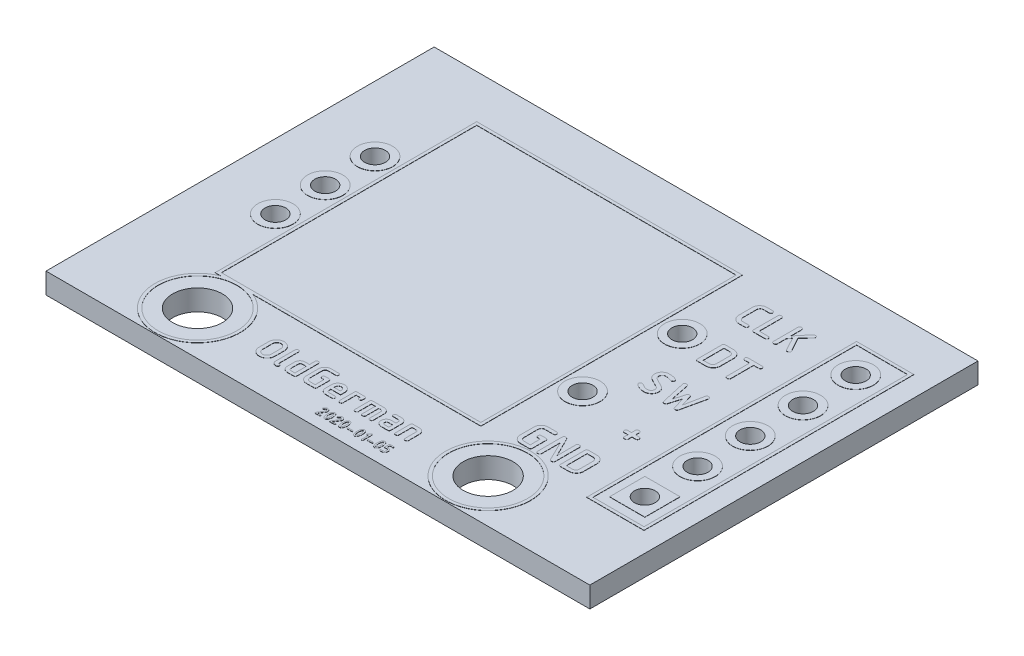
SolidWorks part; units mm, degrees
ref_plane "Front" through (0, 0, 0) normal (0, 0, 1) x (1, 0, 0)
ref_plane "Top" through (0, 0, 0) normal (0, 1, 0) x (1, 0, 0)
ref_plane "Right" through (0, 0, 0) normal (1, 0, 0) x (0, 0, -1)
sketch "草图1" plane through (0, 0, 0) normal (0, 1, 0) x (1, 0, 0)
  line L1 (0, 0) -> (26.2, 0)
  line L2 (0, 0) -> (0, 18.7)
  line L3 (0, 18.7) -> (26.2, 18.7)
  line L4 (26.2, 0) -> (26.2, 18.7)
  circle A0 centre (19.2, 2.1) radius 1.2
  circle A1 centre (5.2, 2.1) radius 1.2
  circle A2 centre (23.85, 5) radius 0.5
  circle A3 centre (23.85, 7.54) radius 0.5
  circle A4 centre (23.85, 10.08) radius 0.5
  circle A5 centre (23.85, 12.62) radius 0.5
  circle A6 centre (23.85, 15.16) radius 0.5
  dimension "D3" = 2.4
  dimension "D4" = 2.4
  dimension "D9" = 1
  dimension "D12" = 5
  dimension "D1" = 26.2
  dimension "D2" = 18.7
  dimension "D5" = 7
  dimension "D6" = 14
  dimension "D7" = 5.2
  dimension "D8" = 16.6
  dimension "D10" = 2.35
  dimension "D11" = 5
extrude "凸台-拉伸1" add sketch "草图1" along normal blind 0.5 and the other way blind 0.5
sketch "草图2" plane through (0, -0.5, 0) normal (0, -1, 0) x (1, 0, 0)
  line L0 (3.15, -7.5) -> (3.15, -13.705) construction
  line L1 (3.25, -7.5) -> (3.05, -7.5) construction
  line L2 (3.05, -7.9) -> (3.8248, -7.9) construction
  line L3 (3.05, -8.3) -> (3.05, -7.5) construction
  line L4 (3.15, -7.9) -> (17.95, -7.9) construction
  line L5 (3.15, -7.9) -> (3.15, -10.3) construction
  circle A0 centre (3.15, -7.9) radius 0.4994
  circle A1 centre (17.95, -7.9) radius 0.4994
  circle A3 centre (17.95, -12.7) radius 0.4994
  circle A4 centre (3.15, -10.3) radius 0.4994
  circle A5 centre (3.15, -12.7) radius 0.4994
  circle A42 centre (17.95, -10.3) radius 0.4994 [skipped]
  dimension "D1" = 0.9989
  dimension "D2" = 2
  dimension "D4" = 14.8
  dimension "D5" = 2.4
  dimension "D3" = 3
extrude "切除-拉伸1" cut sketch "草图2" against normal blind 2
sketch "草图6" plane through (0, 0.5, 0) normal (0, 1, 0) x (1, 0, 0)
  line L1 (24.6991, 4.15) -> (23.0009, 4.15)
  line L2 (24.6991, 4.15) -> (24.6991, 5.85)
  line L3 (24.6991, 5.85) -> (23.0009, 5.85)
  line L4 (23.0009, 4.15) -> (23.0009, 5.85)
  line L5 (24.6991, 4.15) -> (23.0009, 5.85) construction
  line L6 (24.6991, 5.85) -> (23.0009, 4.15) construction
  circle A0 centre (23.85, 15.16) radius 0.85
  circle A1 centre (23.85, 15.16) radius 0.5
  circle A2 centre (23.85, 15.16) radius 0.5
  circle A3 centre (23.85, 12.62) radius 0.5
  circle A4 centre (23.85, 12.62) radius 0.5
  circle A5 centre (23.85, 10.08) radius 0.5
  circle A6 centre (23.85, 10.08) radius 0.5
  circle A7 centre (23.85, 7.54) radius 0.5
  circle A8 centre (23.85, 7.54) radius 0.5
  circle A9 centre (23.85, 5) radius 0.5
  circle A10 centre (23.85, 5) radius 0.5
  circle A11 centre (23.85, 12.62) radius 0.85
  circle A13 centre (23.85, 10.08) radius 0.85
  circle A15 centre (3.15, 7.9) radius 0.4994
  circle A16 centre (3.15, 7.9) radius 0.4994
  circle A17 centre (17.95, 7.9) radius 0.4994
  circle A18 centre (17.95, 7.9) radius 0.4994
  circle A19 centre (17.95, 12.7) radius 0.4994
  circle A20 centre (17.95, 12.7) radius 0.4994
  circle A21 centre (3.15, 10.3) radius 0.4994
  circle A22 centre (3.15, 10.3) radius 0.4994
  circle A23 centre (3.15, 12.7) radius 0.4994
  circle A24 centre (3.15, 12.7) radius 0.4994
  circle A25 centre (23.85, 7.54) radius 0.85
  circle A26 centre (23.85, 5) radius 0.85 construction
  circle A27 centre (3.15, 7.9) radius 0.8494
  circle A28 centre (17.95, 7.9) radius 0.8494
  circle A29 centre (17.95, 12.7) radius 0.8494
  circle A30 centre (3.15, 10.3) radius 0.8494
  circle A31 centre (3.15, 12.7) radius 0.8494
  dimension "D1" = 0
  dimension "D2" = 0
  dimension "D3" = 0
  dimension "D4" = 0
  dimension "D5" = 0
  dimension "D6" = 0.35
  dimension "D8" = 0
  dimension "D9" = 0
  dimension "D10" = 0
  dimension "D11" = 0
  dimension "D12" = 0
extrude "凸台-拉伸4" add sketch "草图6" along normal blind 0.01
mirror "镜向1" about plane through (0, 0, 0) normal (0, 1, 0) of "凸台-拉伸4"
sketch "草图3" plane through (0, 0.5, 0) normal (0, 1, 0) x (1, 0, 0)
  line L1 (16.8, 16.45) -> (4.3, 16.45)
  line L2 (16.8, 16.45) -> (16.8, 4.15)
  line L3 (16.8, 4.15) -> (4.3, 4.15)
  line L4 (4.3, 16.45) -> (4.3, 4.15)
  line L5 (16.8, 16.45) -> (4.3, 4.15) construction
  line L6 (16.8, 4.15) -> (4.3, 16.45) construction
  line L7 (4.55, 10.3) -> (4.55, 5.66) construction
  line L8 (24.77, 16.43) -> (22.97, 16.43) construction
  line L9 (25.08, 3.73) -> (22.62, 3.73)
  line L10 (25.08, 3.73) -> (25.08, 16.43)
  line L11 (25.08, 16.43) -> (22.62, 16.43)
  line L12 (22.62, 3.73) -> (22.62, 16.43)
  line L13 (25.08, 3.73) -> (22.62, 16.43) construction
  line L14 (25.08, 16.43) -> (22.62, 3.73) construction
  line L15 (22.62, 15.96) -> (22.62, 14.36) construction
  line L16 (16.95, 16.6) -> (4.15, 16.6)
  line L17 (4.15, 16.6) -> (4.15, 4)
  line L18 (16.95, 4) -> (5.9697, 4)
  line L19 (16.95, 16.6) -> (16.95, 4)
  line L20 (25.23, 16.58) -> (22.47, 16.58)
  line L21 (22.47, 3.58) -> (22.47, 16.58)
  line L22 (25.23, 3.58) -> (22.47, 3.58)
  line L23 (25.23, 3.58) -> (25.23, 16.58)
  line L24 (4.4303, 4) -> (4.15, 4)
  line L26 (16.95, 4) -> (4.15, 4) construction
  circle A0 centre (5.2, 2.1) radius 1.9
  circle A1 centre (19.2, 2.1) radius 1.9
  arc A2 (4.4303, 4) -> (5.9697, 4) centre (5.2, 2.1) ccw
  circle A3 centre (19.2, 2.1) radius 2.05
  circle A5 centre (5.2, 2.1) radius 2.05 construction
  point P9 (10.55, 10.3)
  point P17 (23.85, 10.08)
  point P37 (7.25, 2.1)
  dimension "D1" = 3.8
  dimension "D3" = 0.25
  dimension "D4" = 0.15
  dimension "D5" = 0.15
  dimension "D2" = 0.15
extrude "凸台-拉伸2" add sketch "草图3" along normal blind 0.01
sketch "草图4" plane through (0, 0.5, 0) normal (0, 1, 0) x (1, 0, 0)
  line L0 (21.4313, 14.4912) -> (-3.813, 14.4912) construction
  text T0 "CLK\r\nDT\r\nSW\r\n+\r\nGND" font "ISOCPEUR" height 1.35
extrude "凸台-拉伸3" add sketch "草图4" along normal blind 0.01
sketch "草图7" plane through (0, 0.5, 0) normal (0, 1, 0) x (1, 0, 0)
  line L0 (5.1646, 1.5809) -> (18.9476, 1.5809) construction
  line L1 (12.0152, 0.543) -> (16.1493, 0.543) construction
  text T0 "OldGerman" font "ISOCPEUR" height 1.2
  text T1 "2020-01-05" font "ISOCPEUR" height 0.5
extrude "凸台-拉伸5" add sketch "草图7" along normal blind 0.01
